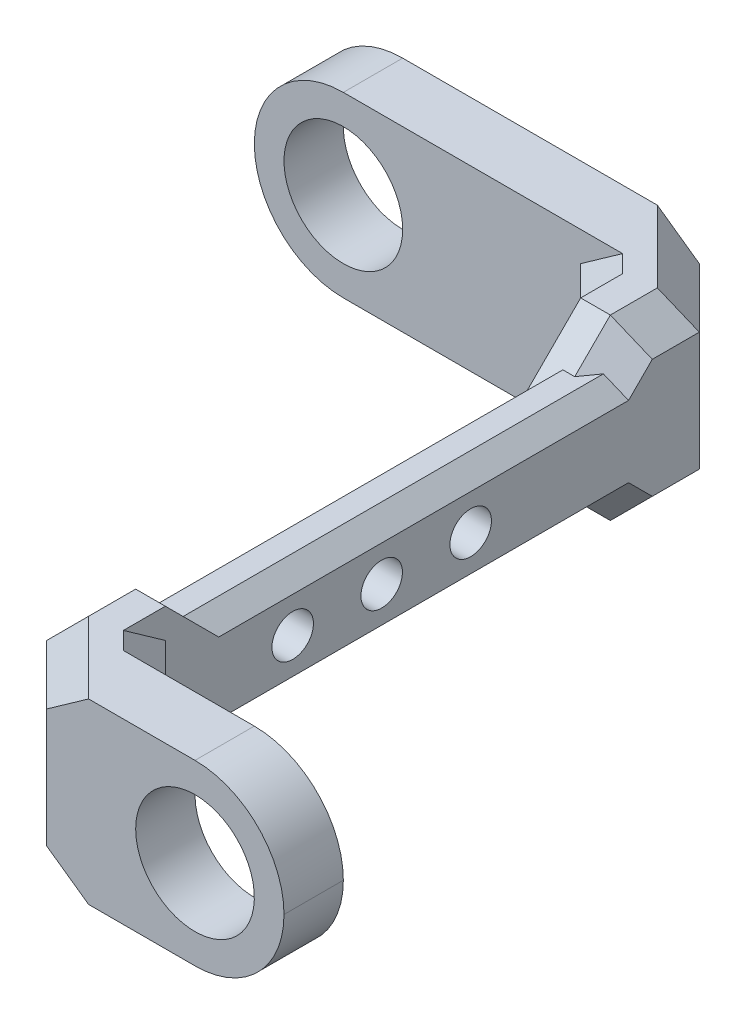
SolidWorks part; units mm, degrees
ref_plane "前视基准面" through (0, 0, 0) normal (0, 0, 1) x (1, 0, 0)
ref_plane "上视基准面" through (0, 0, 0) normal (0, 1, 0) x (1, 0, 0)
ref_plane "右视基准面" through (0, 0, 0) normal (1, 0, 0) x (0, 0, -1)
other "Configuration Table"
sketch "Sketch1" plane through (0, 0, 0) normal (0, 0, 1) x (1, 0, 0)
  line L0 (0, 7.5) -> (30, 7.5)
  line L1 (0, -7.5) -> (30, -7.5)
  line L2 (30, -7.5) -> (30, 7.5)
  circle A0 centre (0, 0) radius 7.5
  circle A1 centre (0, 0) radius 5
  dimension "D1" = 15
  dimension "D2" = 10
  dimension "20" = 30
extrude "Boss-Extrude1" add sketch "Sketch1" along normal blind 5 contours A0 A1 | A0 L1 L2 L0 region at (17.8871, 0, 0) region at (5.1533, 5.1533, 0)
sketch "Sketch2" plane through (0, 0, 5) normal (0, 0, 1) x (1, 0, 0)
  line L0 (0, -7.5) -> (30, -7.5) construction
  line L1 (30, 7.5) -> (25, 7.5)
  line L2 (30, 7.5) -> (30, -7.5)
  line L3 (30, -7.5) -> (25, -7.5)
  line L4 (25, 7.5) -> (25, -7.5)
  dimension "D1" = 5
extrude "Boss-Extrude2" add sketch "Sketch2" along normal blind 55
sketch "Sketch3" plane through (30, 0, 0) normal (1, 0, 0) x (0, 0, -1)
  line L5 (-60, -7.5) -> (0, -7.5) construction
  line L6 (-60, 7.5) -> (-55, 7.5)
  line L7 (-60, 7.5) -> (-60, -7.5)
  line L8 (-60, -7.5) -> (-55, -7.5)
  line L9 (-55, 7.5) -> (-55, -7.5)
  dimension "D1" = 5
extrude "Boss-Extrude3" add sketch "Sketch3" along normal blind 20
sketch "Sketch4" plane through (0, 0, 55) normal (0, 0, -1) x (-1, 0, 0)
  line L0 (-50, 0) -> (-42.5, 0) construction
  line L1 (-50, -7.5) -> (-50, 7.5) construction
  circle A0 centre (-42.5, 0) radius 5
  dimension "D1" = 10
  dimension "D2" = 7.5
extrude "Cut-Extrude1" cut sketch "Sketch4" against normal blind 15
fillet "Fillet1" radius 7.5 2 edges at (50, -7.5, 57.5) (50, 7.5, 57.5)
chamfer "Chamfer1" distance 5 angle 45 4 edges at (30, 0, 0) (25, 0, 5) (25, 0, 60) (30, 0, 55)
sketch "Sketch5" plane through (25, 0, 0) normal (-1, 0, 0) x (0, 0, 1)
  line L0 (10, -7.5) -> (13, -4.5)
  line L1 (13, -4.5) -> (47, -4.5)
  line L2 (47, -4.5) -> (50, -7.5)
  line L3 (55, -7.5) -> (10, -7.5) construction
  line L4 (50, -7.5) -> (10, -7.5)
  line L5 (10, 0) -> (55, 0) construction
  line L6 (10, 7.5) -> (10, -7.5) construction
  line L7 (55, -7.5) -> (55, 7.5) construction
  line L8 (50, 7.5) -> (10, 7.5)
  line L9 (47, 4.5) -> (50, 7.5)
  line L10 (13, 4.5) -> (47, 4.5)
  line L11 (10, 7.5) -> (13, 4.5)
  dimension "D1" = 40
  dimension "D2" = 45
  dimension "D3" = 45
  dimension "D4" = 3
extrude "Cut-Extrude2" cut sketch "Sketch5" against normal blind 5
chamfer "Chamfer2" distance 1.5 angle 45 4 edges at (30, -4.5, 30) (30, 4.5, 30) (25, 4.5, 30) (25, -4.5, 30)
chamfer "Chamfer3" distance 2.5 angle 45 12 edges at (25, 5.25, 47.75) (25, 7.5, 52.5) (27.5, 7.5, 57.5) (25, -5.25, 47.75) (25, -7.5, 52.5) (27.5, -7.5, 57.5) (30, -5.25, 12.25) (30, -7.5, 7.5) (27.5, -7.5, 2.5) (30, 5.25, 12.25) (30, 7.5, 7.5) (27.5, 7.5, 2.5)
chamfer "Chamfer4" distance 2.5 angle 45 4 edges at (22.5, 7.5, 7.5) (22.5, -7.5, 7.5) (32.5, 7.5, 52.5) (32.5, -7.5, 52.5)
sketch "Sketch6" plane through (25, 0, 0) normal (-1, 0, 0) x (0, 0, 1)
  line L0 (31.7678, -3) -> (31.7678, 3) construction
  line L1 (14.5, -3) -> (49.0355, -3) construction
  line L2 (49.0355, 3) -> (14.5, 3) construction
  line L3 (31.7678, 3) -> (31.7678, 0) construction
  line L4 (31.7678, 0) -> (39.2678, 0) construction
  circle A0 centre (31.7678, 0) radius 1.75
  circle A1 centre (39.2678, 0) radius 1.75
  circle A2 centre (24.2678, 0) radius 1.75
  dimension "D1" = 3.5
  dimension "D3" = 3.5
  dimension "D2" = 7.5
extrude "Cut-Extrude3" cut sketch "Sketch6" against normal blind 10
